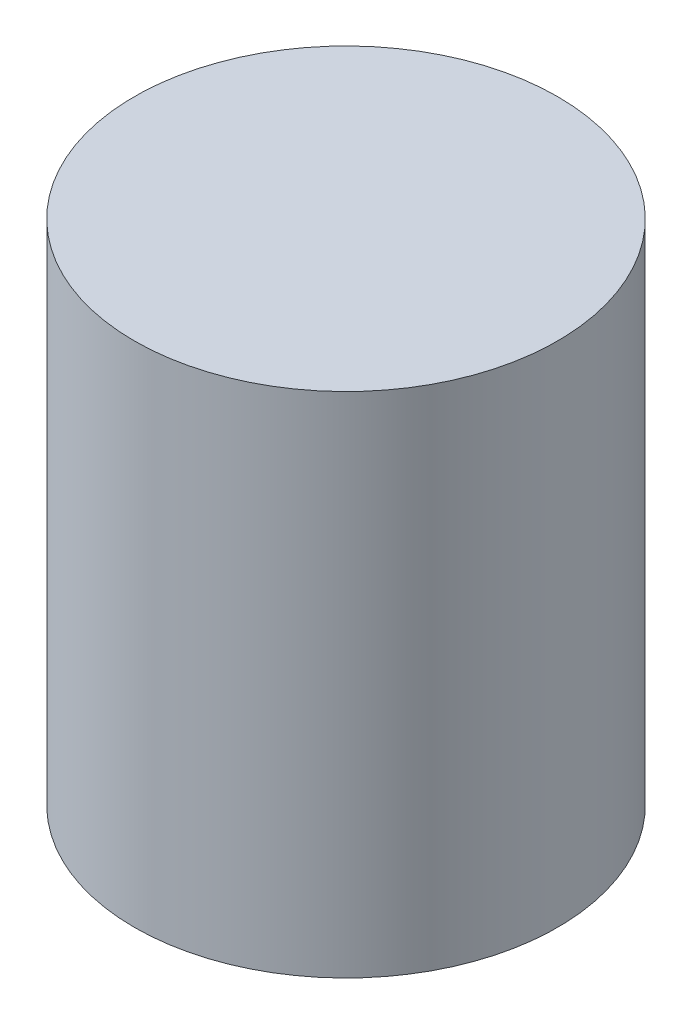
SolidWorks part; units mm, degrees
ref_plane "Front Plane" through (0, 0, 0) normal (0, 0, 1) x (1, 0, 0)
ref_plane "Top Plane" through (0, 0, 0) normal (0, 1, 0) x (1, 0, 0)
ref_plane "Right Plane" through (0, 0, 0) normal (1, 0, 0) x (0, 0, -1)
sketch "Sketch1" plane through (0, 0, 0) normal (0, 1, 0) x (1, 0, 0)
  circle A0 centre (0, 0) radius 10
extrude "Boss-Extrude1" add sketch "Sketch1" along normal mid plane 24 contours A0
scale "Scale1" scale about centroid uniform scaling yes scale factor 0.75
